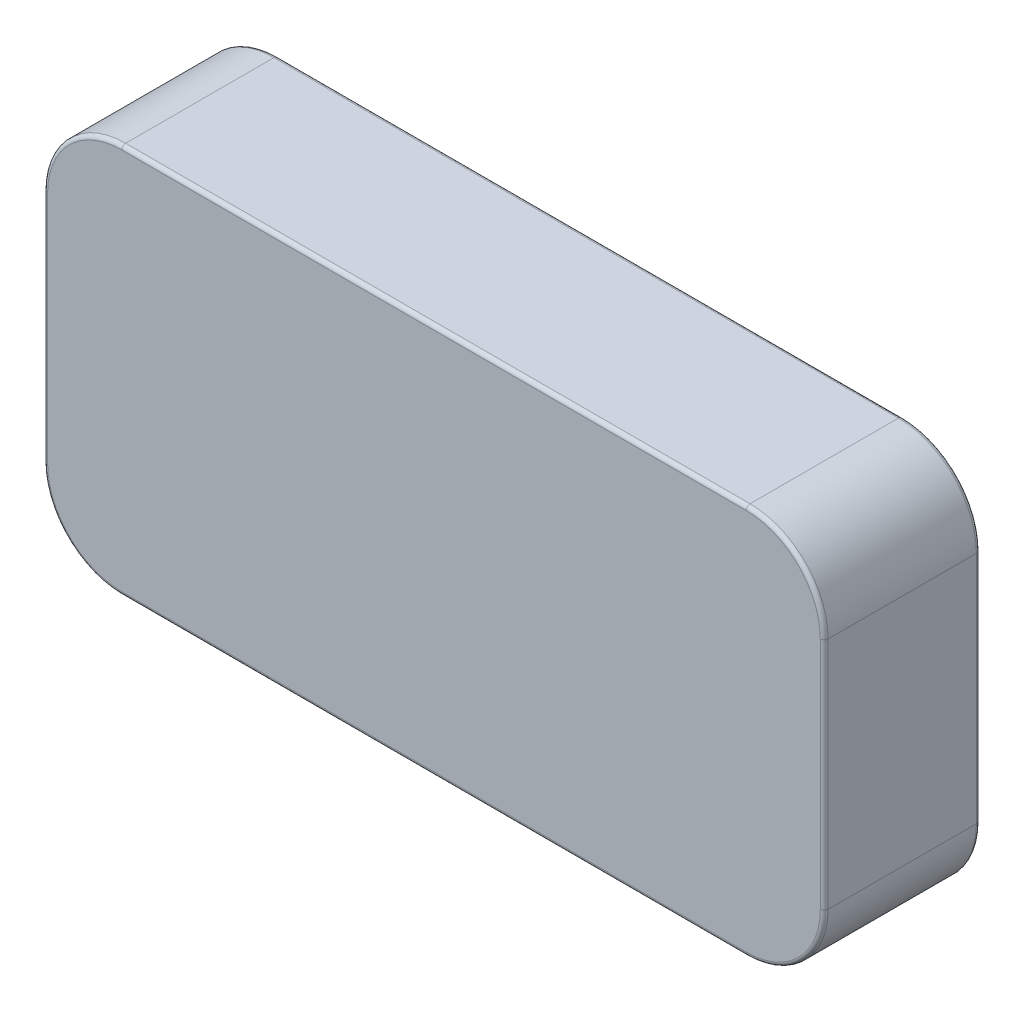
SolidWorks part; units mm, degrees
ref_plane "Front Plane" through (0, 0, 0) normal (0, 0, 1) x (1, 0, 0)
ref_plane "Top Plane" through (0, 0, 0) normal (0, 1, 0) x (1, 0, 0)
ref_plane "Right Plane" through (0, 0, 0) normal (1, 0, 0) x (0, 0, -1)
sketch "Sketch1" plane through (0, 0, 0) normal (0, 0, 1) x (1, 0, 0)
  line L1 (-50, -25) -> (50, -25)
  line L2 (-50, -25) -> (-50, 25)
  line L3 (-50, 25) -> (50, 25)
  line L4 (50, -25) -> (50, 25)
  line L5 (-50, -25) -> (50, 25) construction
  line L6 (-50, 25) -> (50, -25) construction
  point P0 (0, 0)
  dimension "D1" = 100
  dimension "D2" = 50
extrude "Boss-Extrude1" add sketch "Sketch1" along normal blind 20
fillet "Fillet1" radius 10 4 edges at (-50, -25, 10) (50, -25, 10) (50, 25, 10) (-50, 25, 10)
fillet "Fillet2" radius 0.5 16 edges at (47.0711, 22.0711, 0) (50, 0, 0) (47.0711, -22.0711, 0) (0, -25, 0) (-47.0711, -22.0711, 0) (-50, 0, 0) (-47.0711, 22.0711, 0) (47.0711, 22.0711, 20) (50, 0, 20) (47.0711, -22.0711, 20) (0, -25, 20) (-47.0711, -22.0711, 20) (-50, 0, 20) (-47.0711, 22.0711, 20) (0, 25, 0) (0, 25, 20)
